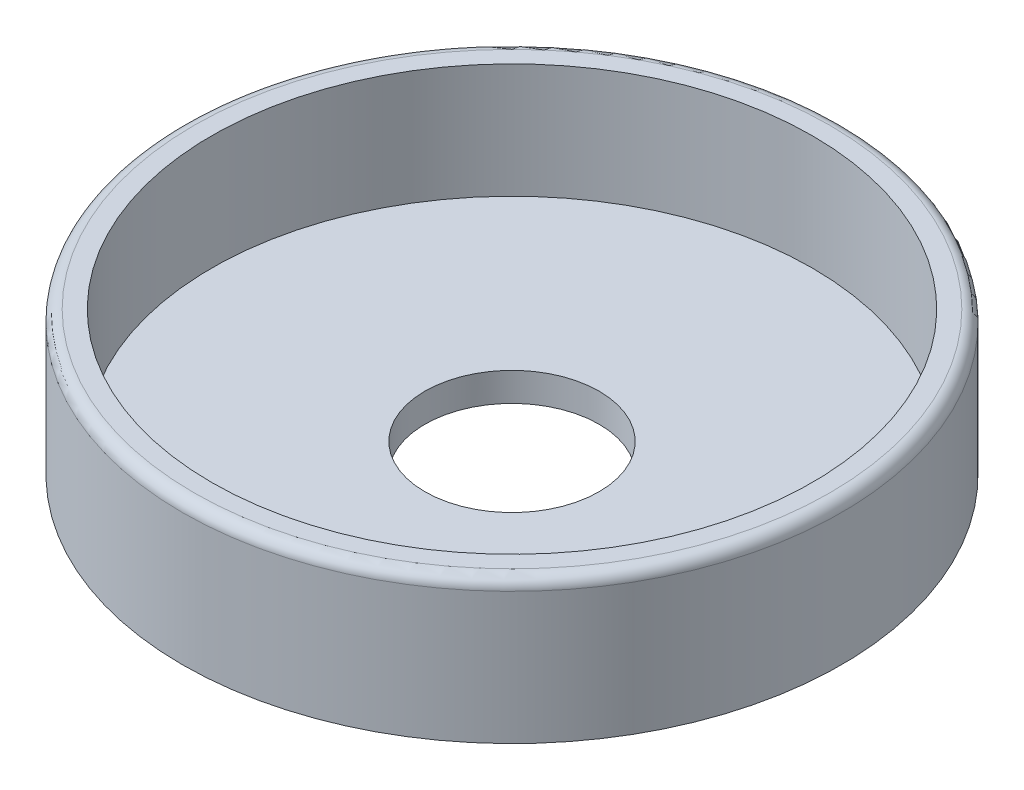
SolidWorks part; units mm, degrees
ref_plane "Front Plane" through (0, 0, 0) normal (0, 0, 1) x (1, 0, 0)
ref_plane "Top Plane" through (0, 0, 0) normal (0, 1, 0) x (1, 0, 0)
ref_plane "Right Plane" through (0, 0, 0) normal (1, 0, 0) x (0, 0, -1)
sketch "Sketch1" plane through (0, 0, 0) normal (0, 1, 0) x (1, 0, 0)
  circle A0 centre (0, 0) radius 73.025
  dimension "D1" = 146.05
extrude "Boss-Extrude1" add sketch "Sketch1" along normal blind 6.35
sketch "Sketch2" plane through (0, 6.35, 0) normal (0, 1, 0) x (1, 0, 0)
  circle A0 centre (0, 0) radius 73.025 construction
  circle A1 centre (0, 0) radius 73.025
  circle A2 centre (0, 0) radius 66.548
  dimension "D1" = 133.096
extrude "Boss-Extrude2" add sketch "Sketch2" along normal blind 25.4
sketch "Sketch3" plane through (0, 0, 0) normal (0, -1, 0) x (1, 0, 0)
  circle A0 centre (0, 0) radius 19.304
  dimension "D1" = 38.608
extrude "Cut-Extrude1" cut sketch "Sketch3" against normal up to next
fillet "Fillet1" radius 2.54 1 edges at (0, 31.75, 73.025)
